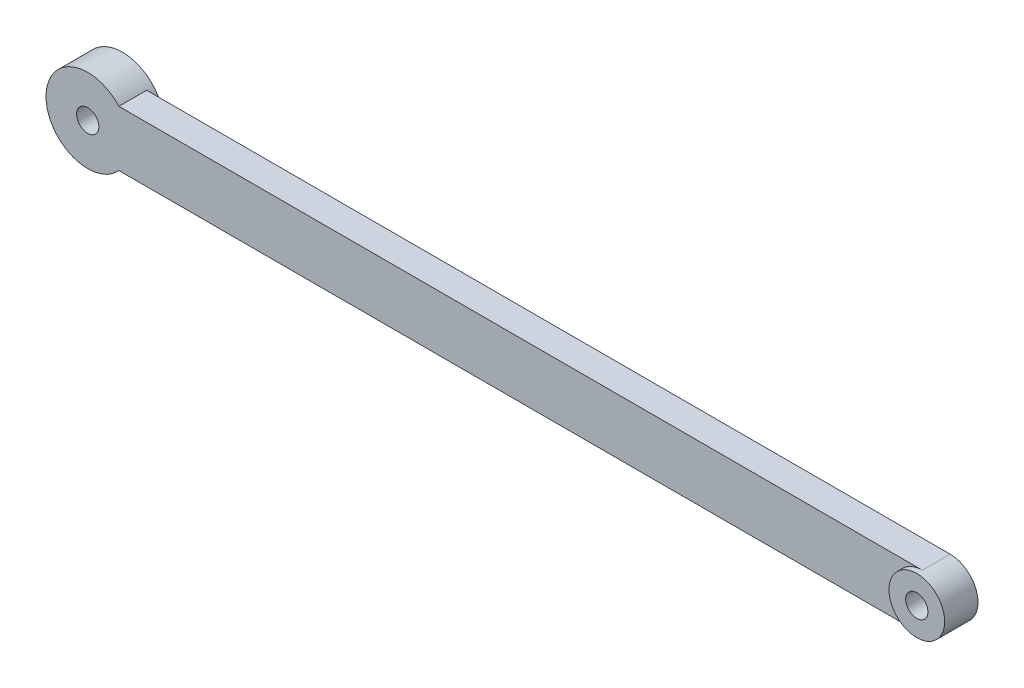
SolidWorks part; units mm, degrees
ref_plane "Ön Düzlem" through (0, 0, 0) normal (0, 0, 1) x (1, 0, 0)
ref_plane "Üst Düzlem" through (0, 0, 0) normal (0, 1, 0) x (1, 0, 0)
ref_plane "Sağ Düzlem" through (0, 0, 0) normal (1, 0, 0) x (0, 0, -1)
sketch "Sketch1" plane through (0, 0, 0) normal (0, 0, 1) x (1, 0, 0)
  line L0 (12.9904, 7.5) -> (293.3856, 7.5)
  line L1 (12.9904, -7.5) -> (293.3856, -7.5)
  circle A0 centre (0, 0) radius 15
  circle A1 centre (300, 0) radius 10
  dimension "D1" = 20
  dimension "D3" = 30
  dimension "D2" = 15
  dimension "D4" = 300
extrude "Boss-Extrude1" add sketch "Sketch1" along normal blind 10 contours A0 | A1 region at (0, 0, 0) region at (300, 0, 0)
sketch "Sketch2" plane through (0, 0, 10) normal (0, 0, 1) x (1, 0, 0)
  circle A1 centre (0, 0) radius 15
  circle A2 centre (0, 0) radius 15
  dimension "D1" = 0
extrude "Boss-Extrude2" [suppressed] add sketch "Sketch2" along normal blind 10 draft 20
sketch "Sketch5" plane through (0, 0, 0) normal (0, 0, 1) x (1, 0, 0)
  line L0 (11.1803, 10) -> (300, 10)
  line L1 (300, -10) -> (11.1803, -10)
  circle A0 centre (0, 0) radius 15 construction
  circle A1 centre (300, 0) radius 10 construction
  circle A2 centre (0, 0) radius 15
  circle A3 centre (300, 0) radius 10
  dimension "D1" = 20
  dimension "D2" = 10
extrude "Boss-Extrude3" add sketch "Sketch5" along normal blind 10 contours A3 L0 A2 L1 region at (152.9795, 0, 0)
sketch "Sketch6" [suppressed] plane through (0, 0, 5) normal (0, 0, 1) x (1, 0, 0)
  circle A1 centre (0, 0) radius 15 construction
  arc A3 (14.7902, -2.5) -> (14.7902, 2.5) centre (0, 0) ccw
extrude "Boss-Extrude4" [suppressed] add sketch "Sketch6" along normal blind 5
sketch "Sketch13" plane through (0, 0, 0) normal (0, 0, -1) x (-1, 0, 0)
  circle A0 centre (-300, 0) radius 4
  circle A1 centre (0, 0) radius 4
extrude "Cut-Extrude1" cut sketch "Sketch13" against normal blind 20
sketch "Sketch14" plane through (0, 0, 0) normal (0, 0, -1) x (-1, 0, 0)
  circle A0 centre (0, 0) radius 4
  circle A1 centre (0, 0) radius 15
extrude "Boss-Extrude7" add sketch "Sketch14" along normal blind 2.5
sketch "Sketch15" plane through (0, 0, 10) normal (0, 0, 1) x (1, 0, 0)
  circle A0 centre (300, 0) radius 4 construction
  arc A1 (300, -10) -> (300, 10) centre (300, 0) ccw construction
  circle A2 centre (300, 0) radius 4
  arc A3 (300, -10) -> (300, 10) centre (300, 0) ccw
  circle A4 centre (300, 0) radius 10
  circle M2 centre (300, 0) radius 4
  arc M3 (300, -10) -> (300, 10) centre (300, 0) ccw
extrude "Boss-Extrude8" add sketch "Sketch15" along normal blind 2 contours A4 M3 M2 region at (290.2828, 0, 10)
